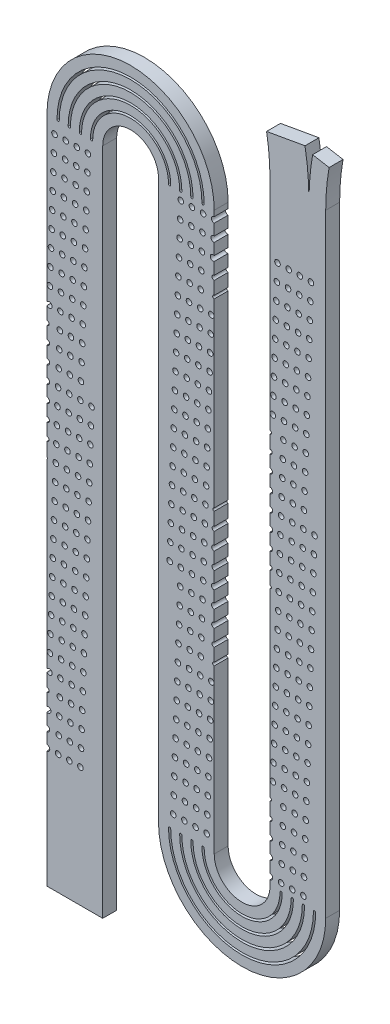
SolidWorks part; units mm, degrees
ref_plane "Front Plane" through (0, 0, 0) normal (0, 0, 1) x (1, 0, 0)
ref_plane "Top Plane" through (0, 0, 0) normal (0, 1, 0) x (1, 0, 0)
ref_plane "Right Plane" through (0, 0, 0) normal (1, 0, 0) x (0, 0, -1)
sketch "Model" plane through (0, 0, 0) normal (0, 0, 1) x (1, 0, 0)
  line L0 (0, 0) -> (0, 0.01)
  line L1 (0, 0.02) -> (0, 0.0401)
  line L2 (0, 0.0499) -> (0, 0.0705)
  line L3 (0, 0.0795) -> (0, 0.1011)
  line L4 (0, 0.1089) -> (0, 0.1323)
  line L5 (0, 0.1377) -> (0, 0.4624)
  line L6 (0, 0.4676) -> (0, 0.4912)
  line L7 (0, 0.4988) -> (0, 0.5205)
  line L8 (0, 0.5295) -> (0, 0.5501)
  line L9 (0, 0.5599) -> (0, 0.58)
  line L10 (0, 0.59) -> (0, 0.6101)
  line L11 (0, 0.6199) -> (0, 0.6404)
  line L12 (0, 0.6496) -> (0, 0.671)
  line L13 (0, 0.679) -> (0, 0.7021)
  line L14 (0, 0.7079) -> (0, 1)
  line L15 (0.1, 0) -> (0.1, 1)
  line L16 (0.3, 1) -> (0.3, 0.99)
  line L17 (0.3, 0.98) -> (0.3, 0.9599)
  line L18 (0.3, 0.9501) -> (0.3, 0.9295)
  line L19 (0.3, 0.9205) -> (0.3, 0.8989)
  line L20 (0.3, 0.8911) -> (0.3, 0.8677)
  line L21 (0.3, 0.8623) -> (0.3, 0.5376)
  line L22 (0.3, 0.5324) -> (0.3, 0.5088)
  line L23 (0.3, 0.5012) -> (0.3, 0.4795)
  line L24 (0.3, 0.4705) -> (0.3, 0.4499)
  line L25 (0.3, 0.4401) -> (0.3, 0.42)
  line L26 (0.3, 0.41) -> (0.3, 0.3899)
  line L27 (0.3, 0.3801) -> (0.3, 0.3596)
  line L28 (0.3, 0.3504) -> (0.3, 0.329)
  line L29 (0.3, 0.321) -> (0.3, 0.2979)
  line L30 (0.3, 0.2921) -> (0.3, 0)
  line L31 (0.2, 1) -> (0.2, 0)
  line L32 (0.4, 0) -> (0.4, 0.01)
  line L33 (0.4, 0.02) -> (0.4, 0.0401)
  line L34 (0.4, 0.0499) -> (0.4, 0.0705)
  line L35 (0.4, 0.0795) -> (0.4, 0.1011)
  line L36 (0.4, 0.1089) -> (0.4, 0.1323)
  line L37 (0.4, 0.1377) -> (0.4, 0.4624)
  line L38 (0.4, 0.4676) -> (0.4, 0.4912)
  line L39 (0.4, 0.4988) -> (0.4, 0.5205)
  line L40 (0.4, 0.5295) -> (0.4, 0.5501)
  line L41 (0.4, 0.5599) -> (0.4, 0.58)
  line L42 (0.4, 0.59) -> (0.4, 0.6101)
  line L43 (0.4, 0.6199) -> (0.4, 0.6404)
  line L44 (0.4, 0.6496) -> (0.4, 0.671)
  line L45 (0.4, 0.679) -> (0.4, 0.7021)
  line L46 (0.4, 0.7079) -> (0.4, 1)
  line L47 (0.5, 0) -> (0.5, 1)
  line L48 (0, 0) -> (0, -0.2)
  line L49 (0.1, 0) -> (0.1, -0.2)
  line L50 (0, -0.2) -> (0.1, -0.2)
  line L51 (0.5061, 1.1695) -> (0.4765, 1.1747)
  line L52 (0.3939, 1.1695) -> (0.4629, 1.1816)
  line L53 (0.4, 1) -> (0.4, 1.1)
  line L54 (0.5, 1) -> (0.5, 1.1)
  arc A0 (0, 0.01) -> (0, 0.02) centre (0, 0.015) ccw
  circle A1 centre (0.02, 0.015) radius 0.005
  circle A2 centre (0.04, 0.015) radius 0.005
  circle A3 centre (0.06, 0.015) radius 0.005
  arc A4 (0, 0.0401) -> (0, 0.0499) centre (0, 0.045) ccw
  circle A5 centre (0.021, 0.045) radius 0.005
  circle A6 centre (0.041, 0.045) radius 0.005
  circle A7 centre (0.061, 0.045) radius 0.005
  arc A8 (0, 0.0705) -> (0, 0.0795) centre (0.0021, 0.075) ccw
  circle A9 centre (0.0221, 0.075) radius 0.005
  circle A10 centre (0.0421, 0.075) radius 0.005
  circle A11 centre (0.0621, 0.075) radius 0.005
  arc A12 (0, 0.1011) -> (0, 0.1089) centre (0, 0.105) ccw
  circle A13 centre (0.0231, 0.105) radius 0.005
  circle A14 centre (0.0431, 0.105) radius 0.005
  circle A15 centre (0.0631, 0.105) radius 0.005
  arc A16 (0, 0.1323) -> (0, 0.1377) centre (0.0042, 0.135) ccw
  circle A17 centre (0.0242, 0.135) radius 0.005
  circle A18 centre (0.0442, 0.135) radius 0.005
  circle A19 centre (0.0642, 0.135) radius 0.005
  circle A20 centre (0.0052, 0.165) radius 0.005
  circle A21 centre (0.0252, 0.165) radius 0.005
  circle A22 centre (0.0452, 0.165) radius 0.005
  circle A23 centre (0.0652, 0.165) radius 0.005
  circle A24 centre (0.0063, 0.195) radius 0.005
  circle A25 centre (0.0263, 0.195) radius 0.005
  circle A26 centre (0.0463, 0.195) radius 0.005
  circle A27 centre (0.0663, 0.195) radius 0.005
  circle A28 centre (0.0073, 0.225) radius 0.005
  circle A29 centre (0.0273, 0.225) radius 0.005
  circle A30 centre (0.0473, 0.225) radius 0.005
  circle A31 centre (0.0673, 0.225) radius 0.005
  circle A32 centre (0.0084, 0.255) radius 0.005
  circle A33 centre (0.0284, 0.255) radius 0.005
  circle A34 centre (0.0484, 0.255) radius 0.005
  circle A35 centre (0.0684, 0.255) radius 0.005
  circle A36 centre (0.0094, 0.285) radius 0.005
  circle A37 centre (0.0294, 0.285) radius 0.005
  circle A38 centre (0.0494, 0.285) radius 0.005
  circle A39 centre (0.0694, 0.285) radius 0.005
  circle A40 centre (0.0105, 0.315) radius 0.005
  circle A41 centre (0.0305, 0.315) radius 0.005
  circle A42 centre (0.0505, 0.315) radius 0.005
  circle A43 centre (0.0705, 0.315) radius 0.005
  circle A44 centre (0.0115, 0.345) radius 0.005
  circle A45 centre (0.0315, 0.345) radius 0.005
  circle A46 centre (0.0515, 0.345) radius 0.005
  circle A47 centre (0.0715, 0.345) radius 0.005
  circle A48 centre (0.0126, 0.375) radius 0.005
  circle A49 centre (0.0326, 0.375) radius 0.005
  circle A50 centre (0.0526, 0.375) radius 0.005
  circle A51 centre (0.0726, 0.375) radius 0.005
  circle A52 centre (0.0136, 0.405) radius 0.005
  circle A53 centre (0.0336, 0.405) radius 0.005
  circle A54 centre (0.0536, 0.405) radius 0.005
  circle A55 centre (0.0736, 0.405) radius 0.005
  circle A56 centre (0.0147, 0.435) radius 0.005
  circle A57 centre (0.0347, 0.435) radius 0.005
  circle A58 centre (0.0547, 0.435) radius 0.005
  circle A59 centre (0.0747, 0.435) radius 0.005
  arc A60 (0, 0.4624) -> (0, 0.4676) centre (-0.0043, 0.465) ccw
  circle A61 centre (0.0157, 0.465) radius 0.005
  circle A62 centre (0.0357, 0.465) radius 0.005
  circle A63 centre (0.0557, 0.465) radius 0.005
  circle A64 centre (0.0757, 0.465) radius 0.005
  arc A65 (0, 0.4912) -> (0, 0.4988) centre (0, 0.495) ccw
  circle A66 centre (0.0168, 0.495) radius 0.005
  circle A67 centre (0.0368, 0.495) radius 0.005
  circle A68 centre (0.0568, 0.495) radius 0.005
  circle A69 centre (0.0768, 0.495) radius 0.005
  arc A70 (0, 0.5205) -> (0, 0.5295) centre (0, 0.525) ccw
  circle A71 centre (0.0178, 0.525) radius 0.005
  circle A72 centre (0.0378, 0.525) radius 0.005
  circle A73 centre (0.0578, 0.525) radius 0.005
  circle A74 centre (0.0778, 0.525) radius 0.005
  arc A75 (0, 0.5501) -> (0, 0.5599) centre (0, 0.555) ccw
  circle A76 centre (0.0189, 0.555) radius 0.005
  circle A77 centre (0.0389, 0.555) radius 0.005
  circle A78 centre (0.0589, 0.555) radius 0.005
  circle A79 centre (0.0789, 0.555) radius 0.005
  arc A80 (0, 0.58) -> (0, 0.59) centre (0, 0.585) ccw
  circle A81 centre (0.0199, 0.585) radius 0.005
  circle A82 centre (0.0399, 0.585) radius 0.005
  circle A83 centre (0.0599, 0.585) radius 0.005
  circle A84 centre (0.0799, 0.585) radius 0.005
  arc A85 (0, 0.6101) -> (0, 0.6199) centre (0, 0.615) ccw
  circle A86 centre (0.021, 0.615) radius 0.005
  circle A87 centre (0.041, 0.615) radius 0.005
  circle A88 centre (0.061, 0.615) radius 0.005
  arc A89 (0, 0.6404) -> (0, 0.6496) centre (0, 0.645) ccw
  circle A90 centre (0.022, 0.645) radius 0.005
  circle A91 centre (0.042, 0.645) radius 0.005
  circle A92 centre (0.062, 0.645) radius 0.005
  arc A93 (0, 0.671) -> (0, 0.679) centre (0, 0.675) ccw
  circle A94 centre (0.023, 0.675) radius 0.005
  circle A95 centre (0.043, 0.675) radius 0.005
  circle A96 centre (0.063, 0.675) radius 0.005
  arc A97 (0, 0.7021) -> (0, 0.7079) centre (0.0041, 0.705) ccw
  circle A98 centre (0.0241, 0.705) radius 0.005
  circle A99 centre (0.0441, 0.705) radius 0.005
  circle A100 centre (0.0641, 0.705) radius 0.005
  circle A101 centre (0.0051, 0.735) radius 0.005
  circle A102 centre (0.0251, 0.735) radius 0.005
  circle A103 centre (0.0451, 0.735) radius 0.005
  circle A104 centre (0.0651, 0.735) radius 0.005
  circle A105 centre (0.0062, 0.765) radius 0.005
  circle A106 centre (0.0262, 0.765) radius 0.005
  circle A107 centre (0.0462, 0.765) radius 0.005
  circle A108 centre (0.0662, 0.765) radius 0.005
  circle A109 centre (0.0072, 0.795) radius 0.005
  circle A110 centre (0.0272, 0.795) radius 0.005
  circle A111 centre (0.0472, 0.795) radius 0.005
  circle A112 centre (0.0672, 0.795) radius 0.005
  circle A113 centre (0.0083, 0.825) radius 0.005
  circle A114 centre (0.0283, 0.825) radius 0.005
  circle A115 centre (0.0483, 0.825) radius 0.005
  circle A116 centre (0.0683, 0.825) radius 0.005
  circle A117 centre (0.0093, 0.855) radius 0.005
  circle A118 centre (0.0293, 0.855) radius 0.005
  circle A119 centre (0.0493, 0.855) radius 0.005
  circle A120 centre (0.0693, 0.855) radius 0.005
  circle A121 centre (0.0104, 0.885) radius 0.005
  circle A122 centre (0.0304, 0.885) radius 0.005
  circle A123 centre (0.0504, 0.885) radius 0.005
  circle A124 centre (0.0704, 0.885) radius 0.005
  circle A125 centre (0.0114, 0.915) radius 0.005
  circle A126 centre (0.0314, 0.915) radius 0.005
  circle A127 centre (0.0514, 0.915) radius 0.005
  circle A128 centre (0.0714, 0.915) radius 0.005
  circle A129 centre (0.0125, 0.945) radius 0.005
  circle A130 centre (0.0325, 0.945) radius 0.005
  circle A131 centre (0.0525, 0.945) radius 0.005
  circle A132 centre (0.0725, 0.945) radius 0.005
  circle A133 centre (0.0135, 0.975) radius 0.005
  circle A134 centre (0.0335, 0.975) radius 0.005
  circle A135 centre (0.0535, 0.975) radius 0.005
  circle A136 centre (0.0735, 0.975) radius 0.005
  arc A137 (0.2, 1) -> (0.1, 1) centre (0.15, 1) ccw
  arc A138 (0.3, 1) -> (0, 1) centre (0.15, 1) ccw
  arc A139 (0.222, 1) -> (0.078, 1) centre (0.15, 1) ccw
  arc A140 (0.242, 1) -> (0.058, 1) centre (0.15, 1) ccw
  arc A141 (0.262, 1) -> (0.038, 1) centre (0.15, 1) ccw
  arc A142 (0.282, 1) -> (0.018, 1) centre (0.15, 1) ccw
  arc A143 (0.218, 1) -> (0.082, 1) centre (0.15, 1) ccw
  arc A144 (0.238, 1) -> (0.062, 1) centre (0.15, 1) ccw
  arc A145 (0.258, 1) -> (0.042, 1) centre (0.15, 1) ccw
  arc A146 (0.278, 1) -> (0.022, 1) centre (0.15, 1) ccw
  arc A147 (0.218, 1) -> (0.222, 1) centre (0.22, 1) ccw
  arc A148 (0.078, 1) -> (0.082, 1) centre (0.08, 1) ccw
  arc A149 (0.238, 1) -> (0.242, 1) centre (0.24, 1) ccw
  arc A150 (0.058, 1) -> (0.062, 1) centre (0.06, 1) ccw
  arc A151 (0.258, 1) -> (0.262, 1) centre (0.26, 1) ccw
  arc A152 (0.038, 1) -> (0.042, 1) centre (0.04, 1) ccw
  arc A153 (0.278, 1) -> (0.282, 1) centre (0.28, 1) ccw
  arc A154 (0.018, 1) -> (0.022, 1) centre (0.02, 1) ccw
  arc A155 (0.3, 0) -> (0.4, 0) centre (0.35, 0) ccw
  arc A156 (0.2, 0) -> (0.5, 0) centre (0.35, 0) ccw
  arc A157 (0.278, 0) -> (0.422, 0) centre (0.35, 0) ccw
  arc A158 (0.258, 0) -> (0.442, 0) centre (0.35, 0) ccw
  arc A159 (0.238, 0) -> (0.462, 0) centre (0.35, 0) ccw
  arc A160 (0.218, 0) -> (0.482, 0) centre (0.35, 0) ccw
  arc A161 (0.282, 0) -> (0.418, 0) centre (0.35, 0) ccw
  arc A162 (0.262, 0) -> (0.438, 0) centre (0.35, 0) ccw
  arc A163 (0.242, 0) -> (0.458, 0) centre (0.35, 0) ccw
  arc A164 (0.222, 0) -> (0.478, 0) centre (0.35, 0) ccw
  arc A165 (0.422, 0) -> (0.418, 0) centre (0.42, 0) ccw
  arc A166 (0.282, 0) -> (0.278, 0) centre (0.28, 0) ccw
  arc A167 (0.442, 0) -> (0.438, 0) centre (0.44, 0) ccw
  arc A168 (0.262, 0) -> (0.258, 0) centre (0.26, 0) ccw
  arc A169 (0.462, 0) -> (0.458, 0) centre (0.46, 0) ccw
  arc A170 (0.242, 0) -> (0.238, 0) centre (0.24, 0) ccw
  arc A171 (0.482, 0) -> (0.478, 0) centre (0.48, 0) ccw
  arc A172 (0.222, 0) -> (0.218, 0) centre (0.22, 0) ccw
  arc A173 (0.3, 0.99) -> (0.3, 0.98) centre (0.3, 0.985) ccw
  circle A174 centre (0.28, 0.985) radius 0.005
  circle A175 centre (0.26, 0.985) radius 0.005
  circle A176 centre (0.24, 0.985) radius 0.005
  arc A177 (0.3, 0.9599) -> (0.3, 0.9501) centre (0.299, 0.955) ccw
  circle A178 centre (0.279, 0.955) radius 0.005
  circle A179 centre (0.259, 0.955) radius 0.005
  circle A180 centre (0.239, 0.955) radius 0.005
  arc A181 (0.3, 0.9295) -> (0.3, 0.9205) centre (0.2979, 0.925) ccw
  circle A182 centre (0.2779, 0.925) radius 0.005
  circle A183 centre (0.2579, 0.925) radius 0.005
  circle A184 centre (0.2379, 0.925) radius 0.005
  arc A185 (0.3, 0.8989) -> (0.3, 0.8911) centre (0.3, 0.895) ccw
  circle A186 centre (0.2769, 0.895) radius 0.005
  circle A187 centre (0.2569, 0.895) radius 0.005
  circle A188 centre (0.2369, 0.895) radius 0.005
  arc A189 (0.3, 0.8677) -> (0.3, 0.8623) centre (0.3, 0.865) ccw
  circle A190 centre (0.2758, 0.865) radius 0.005
  circle A191 centre (0.2558, 0.865) radius 0.005
  circle A192 centre (0.2358, 0.865) radius 0.005
  circle A193 centre (0.2948, 0.835) radius 0.005
  circle A194 centre (0.2748, 0.835) radius 0.005
  circle A195 centre (0.2548, 0.835) radius 0.005
  circle A196 centre (0.2348, 0.835) radius 0.005
  circle A197 centre (0.2937, 0.805) radius 0.005
  circle A198 centre (0.2737, 0.805) radius 0.005
  circle A199 centre (0.2537, 0.805) radius 0.005
  circle A200 centre (0.2337, 0.805) radius 0.005
  circle A201 centre (0.2927, 0.775) radius 0.005
  circle A202 centre (0.2727, 0.775) radius 0.005
  circle A203 centre (0.2527, 0.775) radius 0.005
  circle A204 centre (0.2327, 0.775) radius 0.005
  circle A205 centre (0.2916, 0.745) radius 0.005
  circle A206 centre (0.2716, 0.745) radius 0.005
  circle A207 centre (0.2516, 0.745) radius 0.005
  circle A208 centre (0.2316, 0.745) radius 0.005
  circle A209 centre (0.2906, 0.715) radius 0.005
  circle A210 centre (0.2706, 0.715) radius 0.005
  circle A211 centre (0.2506, 0.715) radius 0.005
  circle A212 centre (0.2306, 0.715) radius 0.005
  circle A213 centre (0.2895, 0.685) radius 0.005
  circle A214 centre (0.2695, 0.685) radius 0.005
  circle A215 centre (0.2495, 0.685) radius 0.005
  circle A216 centre (0.2295, 0.685) radius 0.005
  circle A217 centre (0.2885, 0.655) radius 0.005
  circle A218 centre (0.2685, 0.655) radius 0.005
  circle A219 centre (0.2485, 0.655) radius 0.005
  circle A220 centre (0.2285, 0.655) radius 0.005
  circle A221 centre (0.2874, 0.625) radius 0.005
  circle A222 centre (0.2674, 0.625) radius 0.005
  circle A223 centre (0.2474, 0.625) radius 0.005
  circle A224 centre (0.2274, 0.625) radius 0.005
  circle A225 centre (0.2864, 0.595) radius 0.005
  circle A226 centre (0.2664, 0.595) radius 0.005
  circle A227 centre (0.2464, 0.595) radius 0.005
  circle A228 centre (0.2264, 0.595) radius 0.005
  circle A229 centre (0.2853, 0.565) radius 0.005
  circle A230 centre (0.2653, 0.565) radius 0.005
  circle A231 centre (0.2453, 0.565) radius 0.005
  circle A232 centre (0.2253, 0.565) radius 0.005
  arc A233 (0.3, 0.5376) -> (0.3, 0.5324) centre (0.3, 0.535) ccw
  circle A234 centre (0.2843, 0.535) radius 0.005
  circle A235 centre (0.2643, 0.535) radius 0.005
  circle A236 centre (0.2443, 0.535) radius 0.005
  circle A237 centre (0.2243, 0.535) radius 0.005
  arc A238 (0.3, 0.5088) -> (0.3, 0.5012) centre (0.3, 0.505) ccw
  circle A239 centre (0.2832, 0.505) radius 0.005
  circle A240 centre (0.2632, 0.505) radius 0.005
  circle A241 centre (0.2432, 0.505) radius 0.005
  circle A242 centre (0.2232, 0.505) radius 0.005
  arc A243 (0.3, 0.4795) -> (0.3, 0.4705) centre (0.3, 0.475) ccw
  circle A244 centre (0.2822, 0.475) radius 0.005
  circle A245 centre (0.2622, 0.475) radius 0.005
  circle A246 centre (0.2422, 0.475) radius 0.005
  circle A247 centre (0.2222, 0.475) radius 0.005
  arc A248 (0.3, 0.4499) -> (0.3, 0.4401) centre (0.3011, 0.445) ccw
  circle A249 centre (0.2811, 0.445) radius 0.005
  circle A250 centre (0.2611, 0.445) radius 0.005
  circle A251 centre (0.2411, 0.445) radius 0.005
  circle A252 centre (0.2211, 0.445) radius 0.005
  arc A253 (0.3, 0.42) -> (0.3, 0.41) centre (0.3, 0.415) ccw
  circle A254 centre (0.2801, 0.415) radius 0.005
  circle A255 centre (0.2601, 0.415) radius 0.005
  circle A256 centre (0.2401, 0.415) radius 0.005
  circle A257 centre (0.2201, 0.415) radius 0.005
  arc A258 (0.3, 0.3899) -> (0.3, 0.3801) centre (0.3, 0.385) ccw
  circle A259 centre (0.279, 0.385) radius 0.005
  circle A260 centre (0.259, 0.385) radius 0.005
  circle A261 centre (0.239, 0.385) radius 0.005
  arc A262 (0.3, 0.3596) -> (0.3, 0.3504) centre (0.3, 0.355) ccw
  circle A263 centre (0.278, 0.355) radius 0.005
  circle A264 centre (0.258, 0.355) radius 0.005
  circle A265 centre (0.238, 0.355) radius 0.005
  arc A266 (0.3, 0.329) -> (0.3, 0.321) centre (0.3, 0.325) ccw
  circle A267 centre (0.277, 0.325) radius 0.005
  circle A268 centre (0.257, 0.325) radius 0.005
  circle A269 centre (0.237, 0.325) radius 0.005
  arc A270 (0.3, 0.2979) -> (0.3, 0.2921) centre (0.3, 0.295) ccw
  circle A271 centre (0.2759, 0.295) radius 0.005
  circle A272 centre (0.2559, 0.295) radius 0.005
  circle A273 centre (0.2359, 0.295) radius 0.005
  circle A274 centre (0.2949, 0.265) radius 0.005
  circle A275 centre (0.2749, 0.265) radius 0.005
  circle A276 centre (0.2549, 0.265) radius 0.005
  circle A277 centre (0.2349, 0.265) radius 0.005
  circle A278 centre (0.2938, 0.235) radius 0.005
  circle A279 centre (0.2738, 0.235) radius 0.005
  circle A280 centre (0.2538, 0.235) radius 0.005
  circle A281 centre (0.2338, 0.235) radius 0.005
  circle A282 centre (0.2928, 0.205) radius 0.005
  circle A283 centre (0.2728, 0.205) radius 0.005
  circle A284 centre (0.2528, 0.205) radius 0.005
  circle A285 centre (0.2328, 0.205) radius 0.005
  circle A286 centre (0.2917, 0.175) radius 0.005
  circle A287 centre (0.2717, 0.175) radius 0.005
  circle A288 centre (0.2517, 0.175) radius 0.005
  circle A289 centre (0.2317, 0.175) radius 0.005
  circle A290 centre (0.2907, 0.145) radius 0.005
  circle A291 centre (0.2707, 0.145) radius 0.005
  circle A292 centre (0.2507, 0.145) radius 0.005
  circle A293 centre (0.2307, 0.145) radius 0.005
  circle A294 centre (0.2896, 0.115) radius 0.005
  circle A295 centre (0.2696, 0.115) radius 0.005
  circle A296 centre (0.2496, 0.115) radius 0.005
  circle A297 centre (0.2296, 0.115) radius 0.005
  circle A298 centre (0.2886, 0.085) radius 0.005
  circle A299 centre (0.2686, 0.085) radius 0.005
  circle A300 centre (0.2486, 0.085) radius 0.005
  circle A301 centre (0.2286, 0.085) radius 0.005
  circle A302 centre (0.2875, 0.055) radius 0.005
  circle A303 centre (0.2675, 0.055) radius 0.005
  circle A304 centre (0.2475, 0.055) radius 0.005
  circle A305 centre (0.2275, 0.055) radius 0.005
  circle A306 centre (0.2865, 0.025) radius 0.005
  circle A307 centre (0.2665, 0.025) radius 0.005
  circle A308 centre (0.2465, 0.025) radius 0.005
  circle A309 centre (0.2265, 0.025) radius 0.005
  arc A310 (0.4, 0.01) -> (0.4, 0.02) centre (0.4, 0.015) ccw
  circle A311 centre (0.42, 0.015) radius 0.005
  circle A312 centre (0.44, 0.015) radius 0.005
  circle A313 centre (0.46, 0.015) radius 0.005
  arc A314 (0.4, 0.0401) -> (0.4, 0.0499) centre (0.4, 0.045) ccw
  circle A315 centre (0.421, 0.045) radius 0.005
  circle A316 centre (0.441, 0.045) radius 0.005
  circle A317 centre (0.461, 0.045) radius 0.005
  arc A318 (0.4, 0.0705) -> (0.4, 0.0795) centre (0.4, 0.075) ccw
  circle A319 centre (0.4221, 0.075) radius 0.005
  circle A320 centre (0.4421, 0.075) radius 0.005
  circle A321 centre (0.4621, 0.075) radius 0.005
  arc A322 (0.4, 0.1011) -> (0.4, 0.1089) centre (0.4, 0.105) ccw
  circle A323 centre (0.4231, 0.105) radius 0.005
  circle A324 centre (0.4431, 0.105) radius 0.005
  circle A325 centre (0.4631, 0.105) radius 0.005
  arc A326 (0.4, 0.1323) -> (0.4, 0.1377) centre (0.4, 0.135) ccw
  circle A327 centre (0.4242, 0.135) radius 0.005
  circle A328 centre (0.4442, 0.135) radius 0.005
  circle A329 centre (0.4642, 0.135) radius 0.005
  circle A330 centre (0.4052, 0.165) radius 0.005
  circle A331 centre (0.4252, 0.165) radius 0.005
  circle A332 centre (0.4452, 0.165) radius 0.005
  circle A333 centre (0.4652, 0.165) radius 0.005
  circle A334 centre (0.4063, 0.195) radius 0.005
  circle A335 centre (0.4263, 0.195) radius 0.005
  circle A336 centre (0.4463, 0.195) radius 0.005
  circle A337 centre (0.4663, 0.195) radius 0.005
  circle A338 centre (0.4073, 0.225) radius 0.005
  circle A339 centre (0.4273, 0.225) radius 0.005
  circle A340 centre (0.4473, 0.225) radius 0.005
  circle A341 centre (0.4673, 0.225) radius 0.005
  circle A342 centre (0.4084, 0.255) radius 0.005
  circle A343 centre (0.4284, 0.255) radius 0.005
  circle A344 centre (0.4484, 0.255) radius 0.005
  circle A345 centre (0.4684, 0.255) radius 0.005
  circle A346 centre (0.4094, 0.285) radius 0.005
  circle A347 centre (0.4294, 0.285) radius 0.005
  circle A348 centre (0.4494, 0.285) radius 0.005
  circle A349 centre (0.4694, 0.285) radius 0.005
  circle A350 centre (0.4105, 0.315) radius 0.005
  circle A351 centre (0.4305, 0.315) radius 0.005
  circle A352 centre (0.4505, 0.315) radius 0.005
  circle A353 centre (0.4705, 0.315) radius 0.005
  circle A354 centre (0.4115, 0.345) radius 0.005
  circle A355 centre (0.4315, 0.345) radius 0.005
  circle A356 centre (0.4515, 0.345) radius 0.005
  circle A357 centre (0.4715, 0.345) radius 0.005
  circle A358 centre (0.4126, 0.375) radius 0.005
  circle A359 centre (0.4326, 0.375) radius 0.005
  circle A360 centre (0.4526, 0.375) radius 0.005
  circle A361 centre (0.4726, 0.375) radius 0.005
  circle A362 centre (0.4136, 0.405) radius 0.005
  circle A363 centre (0.4336, 0.405) radius 0.005
  circle A364 centre (0.4536, 0.405) radius 0.005
  circle A365 centre (0.4736, 0.405) radius 0.005
  circle A366 centre (0.4147, 0.435) radius 0.005
  circle A367 centre (0.4347, 0.435) radius 0.005
  circle A368 centre (0.4547, 0.435) radius 0.005
  circle A369 centre (0.4747, 0.435) radius 0.005
  arc A370 (0.4, 0.4624) -> (0.4, 0.4676) centre (0.4, 0.465) ccw
  circle A371 centre (0.4157, 0.465) radius 0.005
  circle A372 centre (0.4357, 0.465) radius 0.005
  circle A373 centre (0.4557, 0.465) radius 0.005
  circle A374 centre (0.4757, 0.465) radius 0.005
  arc A375 (0.4, 0.4912) -> (0.4, 0.4988) centre (0.4, 0.495) ccw
  circle A376 centre (0.4168, 0.495) radius 0.005
  circle A377 centre (0.4368, 0.495) radius 0.005
  circle A378 centre (0.4568, 0.495) radius 0.005
  circle A379 centre (0.4768, 0.495) radius 0.005
  arc A380 (0.4, 0.5205) -> (0.4, 0.5295) centre (0.4, 0.525) ccw
  circle A381 centre (0.4178, 0.525) radius 0.005
  circle A382 centre (0.4378, 0.525) radius 0.005
  circle A383 centre (0.4578, 0.525) radius 0.005
  circle A384 centre (0.4778, 0.525) radius 0.005
  arc A385 (0.4, 0.5501) -> (0.4, 0.5599) centre (0.4, 0.555) ccw
  circle A386 centre (0.4189, 0.555) radius 0.005
  circle A387 centre (0.4389, 0.555) radius 0.005
  circle A388 centre (0.4589, 0.555) radius 0.005
  circle A389 centre (0.4789, 0.555) radius 0.005
  arc A390 (0.4, 0.58) -> (0.4, 0.59) centre (0.3999, 0.585) ccw
  circle A391 centre (0.4199, 0.585) radius 0.005
  circle A392 centre (0.4399, 0.585) radius 0.005
  circle A393 centre (0.4599, 0.585) radius 0.005
  circle A394 centre (0.4799, 0.585) radius 0.005
  arc A395 (0.4, 0.6101) -> (0.4, 0.6199) centre (0.4, 0.615) ccw
  circle A396 centre (0.421, 0.615) radius 0.005
  circle A397 centre (0.441, 0.615) radius 0.005
  circle A398 centre (0.461, 0.615) radius 0.005
  arc A399 (0.4, 0.6404) -> (0.4, 0.6496) centre (0.4, 0.645) ccw
  circle A400 centre (0.422, 0.645) radius 0.005
  circle A401 centre (0.442, 0.645) radius 0.005
  circle A402 centre (0.462, 0.645) radius 0.005
  arc A403 (0.4, 0.671) -> (0.4, 0.679) centre (0.4, 0.675) ccw
  circle A404 centre (0.423, 0.675) radius 0.005
  circle A405 centre (0.443, 0.675) radius 0.005
  circle A406 centre (0.463, 0.675) radius 0.005
  arc A407 (0.4, 0.7021) -> (0.4, 0.7079) centre (0.4, 0.705) ccw
  circle A408 centre (0.4241, 0.705) radius 0.005
  circle A409 centre (0.4441, 0.705) radius 0.005
  circle A410 centre (0.4641, 0.705) radius 0.005
  circle A411 centre (0.4051, 0.735) radius 0.005
  circle A412 centre (0.4251, 0.735) radius 0.005
  circle A413 centre (0.4451, 0.735) radius 0.005
  circle A414 centre (0.4651, 0.735) radius 0.005
  circle A415 centre (0.4062, 0.765) radius 0.005
  circle A416 centre (0.4262, 0.765) radius 0.005
  circle A417 centre (0.4462, 0.765) radius 0.005
  circle A418 centre (0.4662, 0.765) radius 0.005
  circle A419 centre (0.4072, 0.795) radius 0.005
  circle A420 centre (0.4272, 0.795) radius 0.005
  circle A421 centre (0.4472, 0.795) radius 0.005
  circle A422 centre (0.4672, 0.795) radius 0.005
  circle A423 centre (0.4083, 0.825) radius 0.005
  circle A424 centre (0.4283, 0.825) radius 0.005
  circle A425 centre (0.4483, 0.825) radius 0.005
  circle A426 centre (0.4683, 0.825) radius 0.005
  circle A427 centre (0.4093, 0.855) radius 0.005
  circle A428 centre (0.4293, 0.855) radius 0.005
  circle A429 centre (0.4493, 0.855) radius 0.005
  circle A430 centre (0.4693, 0.855) radius 0.005
  circle A431 centre (0.4104, 0.885) radius 0.005
  circle A432 centre (0.4304, 0.885) radius 0.005
  circle A433 centre (0.4504, 0.885) radius 0.005
  circle A434 centre (0.4704, 0.885) radius 0.005
  circle A435 centre (0.4114, 0.915) radius 0.005
  circle A436 centre (0.4314, 0.915) radius 0.005
  circle A437 centre (0.4514, 0.915) radius 0.005
  circle A438 centre (0.4714, 0.915) radius 0.005
  circle A439 centre (0.4125, 0.945) radius 0.005
  circle A440 centre (0.4325, 0.945) radius 0.005
  circle A441 centre (0.4525, 0.945) radius 0.005
  circle A442 centre (0.4725, 0.945) radius 0.005
  circle A443 centre (0.4135, 0.975) radius 0.005
  circle A444 centre (0.4335, 0.975) radius 0.005
  circle A445 centre (0.4535, 0.975) radius 0.005
  circle A446 centre (0.4735, 0.975) radius 0.005
  arc A447 (0.5061, 1.1695) -> (0.5, 1.1) centre (0.9, 1.1) ccw
  arc A448 (0.4765, 1.1747) -> (0.47, 1.1) centre (0.9, 1.1) ccw
  arc A449 (0.4, 1.1) -> (0.3939, 1.1695) centre (0, 1.1) ccw
  arc A450 (0.47, 1.1) -> (0.4629, 1.1816) centre (0, 1.1) ccw
extrude "Boss-Extrude1" add sketch "Model" along normal blind 0.025
